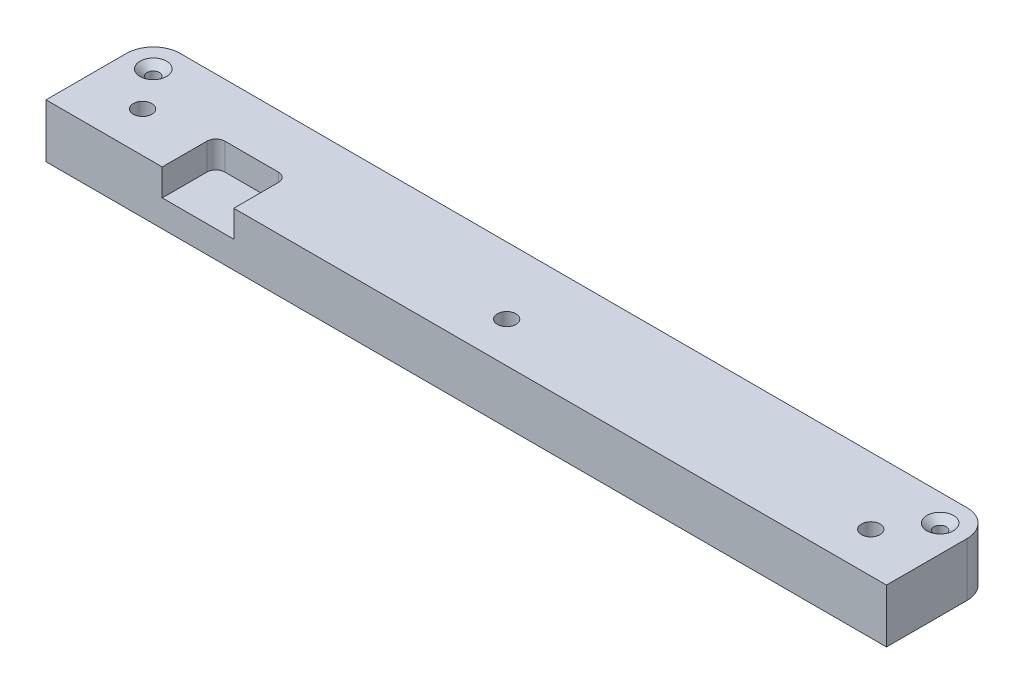
SolidWorks part; units mm, degrees
ref_plane "Front Plane" through (0, 0, 0) normal (0, 0, 1) x (1, 0, 0)
ref_plane "Top Plane" through (0, 0, 0) normal (0, 1, 0) x (1, 0, 0)
ref_plane "Right Plane" through (0, 0, 0) normal (1, 0, 0) x (0, 0, -1)
sketch "Sketch1" plane through (0, 0, 0) normal (0, 1, 0) x (1, 0, 0)
  line L1 (0, 0) -> (298.45, 0)
  line L2 (0, 0) -> (0, 38.1)
  line L3 (0, 38.1) -> (298.45, 38.1)
  line L4 (298.45, 0) -> (298.45, 38.1)
  dimension "D1" = 38.1
  dimension "D2" = 298.45
extrude "Boss-Extrude1" add sketch "Sketch1" along normal blind 19.05
fillet "Fillet1" radius 9.525 2 edges at (298.45, 9.525, -38.1) (0, 9.525, -38.1)
sketch "Sketch2" plane through (0, 19.05, 0) normal (0, 1, 0) x (1, 0, 0)
  line L0 (0, 14.351) -> (298.45, 14.351) construction
  line L1 (0, 28.575) -> (0, 0) construction
  line L2 (298.45, 0) -> (298.45, 28.575) construction
  line L3 (288.925, 38.1) -> (9.525, 38.1) construction
  circle A0 centre (19.939, 14.351) radius 3.302
  circle A1 centre (149.225, 14.351) radius 3.302
  circle A2 centre (278.511, 14.351) radius 3.302
  dimension "D2" = 6.604
  dimension "D1" = 23.749
  dimension "D3" = 19.939
  dimension "D4" = 19.939
extrude "Cut-Extrude1" cut sketch "Sketch2" against normal blind 14.2875
sketch "Sketch4" plane through (0, 0, 0) normal (0, -1, 0) x (1, 0, 0)
  circle A0 centre (19.939, -14.351) radius 1.4224
  circle A1 centre (149.225, -14.351) radius 1.4224
  circle A2 centre (278.511, -14.351) radius 1.4224
  dimension "D1" = 2.8448
extrude "Cut-Extrude2" cut sketch "Sketch4" against normal through all
sketch "Sketch5" plane through (0, 0, 0) normal (0, -1, 0) x (1, 0, 0)
  circle A0 centre (19.939, -14.351) radius 2.413
  circle A1 centre (149.225, -14.351) radius 2.413
  circle A2 centre (278.511, -14.351) radius 2.413
  dimension "D1" = 4.826
extrude "Cut-Extrude3" cut sketch "Sketch5" against normal blind 2.921
sketch "Sketch6" plane through (0, 19.05, 0) normal (0, 1, 0) x (1, 0, 0)
  line L0 (298.45, 28.575) -> (0, 28.575) construction
  line L1 (0, 28.575) -> (0, 0) construction
  line L2 (298.45, 0) -> (298.45, 28.575) construction
  circle A0 centre (9.525, 28.575) radius 2.1844
  circle A1 centre (288.925, 28.575) radius 2.1844
  dimension "D3" = 4.3688
  dimension "D1" = 9.525
  dimension "D2" = 9.525
extrude "Cut-Extrude4" cut sketch "Sketch6" against normal through all contours L0 A1 | A1 L0 | A0 region at (288.925, 19.05, -27.6479) region at (288.925, 19.05, -29.5021)
chamfer "Chamfer1" distance 2.54 angle 41 2 edges at (288.925, 19.05, -26.3906) (9.525, 19.05, -26.3906) first distance on face at (9.525, 19.05, -26.3906)
sketch "Sketch7" plane through (0, 19.05, 0) normal (0, 1, 0) x (1, 0, 0)
  line L0 (288.925, 38.1) -> (9.525, 38.1) construction
  circle A0 centre (149.225, 28.575) radius 7.239
  dimension "D2" = 14.478
  dimension "D1" = 9.525
extrude "Cut-Extrude5" cut sketch "Sketch7" against normal through all from offset 5.08 offset against normal yes
sketch "Sketch8" plane through (0, 0, 0) normal (0, -1, 0) x (1, 0, 0)
  line L0 (0, 0) -> (298.45, 0) construction
  line L1 (41.275, 0) -> (66.675, 0)
  line L2 (41.275, 0) -> (41.275, -19.05)
  line L3 (41.275, -19.05) -> (66.675, -19.05)
  line L4 (66.675, 0) -> (66.675, -19.05)
  line L5 (0, -28.575) -> (0, 0) construction
  dimension "D1" = 41.275
  dimension "D2" = 25.4
  dimension "D3" = 19.05
extrude "Cut-Extrude6" cut sketch "Sketch8" against normal blind 9.525 from offset 9.525 offset against normal yes
fillet "Fillet2" radius 3.175 2 edges at (66.675, 14.2875, -19.05) (41.275, 14.2875, -19.05)
